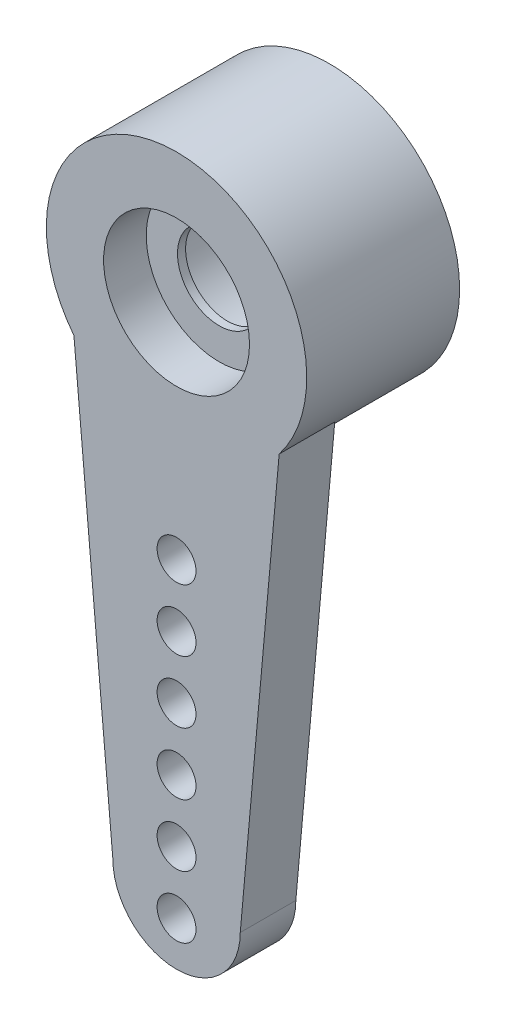
SolidWorks part; units mm, degrees
material "Nylon 6/10"
ref_plane "Front Plane" through (0, 0, 0) normal (0, 0, 1) x (1, 0, 0)
ref_plane "Top Plane" through (0, 0, 0) normal (0, 1, 0) x (1, 0, 0)
ref_plane "Right Plane" through (0, 0, 0) normal (1, 0, 0) x (0, 0, -1)
ref_plane "Plane1" through (0, 0, -7.033) normal (0, 0, 1) x (1, 0, 0)
sketch "Sketch1" plane through (0, 0, -7.033) normal (0, 0, 1) x (1, 0, 0)
  circle A0 centre (-5.5, 0) radius 3.5687
  circle A1 centre (-5.5, 0) radius 2
  dimension "D1" = 7.1374
extrude "Boss-Extrude1" add sketch "Sketch1" along normal blind 4.191
sketch "Sketch5" plane through (0, 0, -4.233) normal (0, 0, 1) x (1, 0, 0)
  circle A0 centre (-5.5, 0) radius 1.143
  circle A1 centre (-5.5, 0) radius 2 construction
  circle A2 centre (-5.5, 0) radius 2
  dimension "D1" = 2.286
extrude "Boss-Extrude2" add sketch "Sketch5" along normal offset from surface (0.2226 mm away) 1.1684 up to face at (-1.9313, 0, -2.842)
sketch "Sketch6" plane through (0, 0, -2.842) normal (0, 0, 1) x (1, 0, 0)
  line L0 (-3.7537, -14.0907) -> (-2.6869, -2.196)
  line L1 (-7.2462, -14.0907) -> (-8.313, -2.196)
  line L2 (-5.5, 0) -> (-5.5, -14.0907) construction
  line L3 (-5.5, -14.6241) -> (-5.5, -12.9223) construction
  arc A0 (-7.2462, -14.0907) -> (-3.7537, -14.0907) centre (-5.5, -14.0907) ccw
  circle A1 centre (-5.5, 0) radius 3.5687 construction
  circle A2 centre (-5.5, 0) radius 3.5687 construction
  circle A3 centre (-5.5, -12.9223) radius 0.5334
  circle A4 centre (-5.5, -14.6241) radius 0.5334
  circle A5 centre (-5.5, -11.2205) radius 0.5334
  circle A6 centre (-5.5, -9.5186) radius 0.5334
  circle A7 centre (-5.5, -7.8169) radius 0.5334
  circle A8 centre (-5.5, -6.1151) radius 0.5334
  arc A9 (-2.6869, -2.196) -> (-8.313, -2.196) centre (-5.5, 0) cw
  dimension "D1" = 3.4925
  dimension "D2" = 15.8369
  dimension "D4" = 1.0668
  dimension "D3" = 5.6261
  dimension "D6" = 1.7018
  dimension "D5" = 6
extrude "Boss-Extrude3" add sketch "Sketch6" against normal blind 1.524
scale "Scale1" bodies to scale 103 scale about centroid uniform scaling yes scale factor 0.1
sketch "Sketch9" plane through (0, 0, -4.6762) normal (0, 0, -1) x (-1, 0, 0)
  line L0 (5.5, -2.6465) -> (5.5, -4.4124)
  circle A0 centre (5.5, -3.0033) radius 0.3569 construction
ref_plane "Plane2" through (-5.5, 0, 0) normal (1, 0, 0) x (0, -1, 0)
